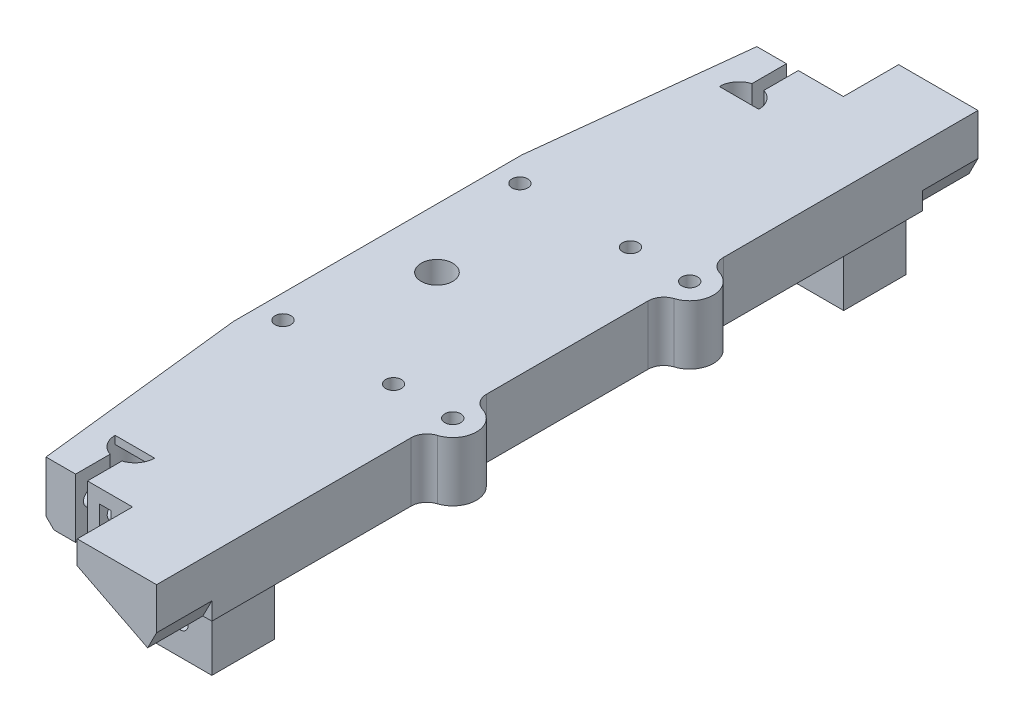
SolidWorks part; units mm, degrees
ref_plane "Płaszczyzna przednia" through (0, 0, 0) normal (0, 0, 1) x (1, 0, 0)
ref_plane "Płaszczyzna górna" through (0, 0, 0) normal (0, 1, 0) x (1, 0, 0)
ref_plane "Płaszczyzna prawa" through (0, 0, 0) normal (1, 0, 0) x (0, 0, -1)
sketch "Szkic1" plane through (0, 0, 0) normal (0, 1, 0) x (1, 0, 0)
  line L0 (-20.5, 36.5) -> (-14.5, 90)
  line L1 (27.5, -90) -> (-14.5, -90)
  line L2 (27.5, -90) -> (27.5, 90)
  line L3 (27.5, 90) -> (-14.5, 90)
  line L4 (-20.5, -36.5) -> (-20.5, 36.5)
  line L5 (27.5, 0) -> (-46.9742, 0) construction
  line L6 (-7, -81.2697) -> (-7, -90)
  line L7 (-20.5, -36.5) -> (-14.5, -90)
  line L8 (-4, -81.2697) -> (-4, -90)
  line L9 (-7, 81.2697) -> (-7, 90)
  line L10 (-4, 81.2697) -> (-4, 90)
  circle A0 centre (-14.5, 30) radius 2
  circle A1 centre (13.5, 30) radius 2
  circle A4 centre (13.5, -30) radius 2
  circle A5 centre (-14.5, -30) radius 2
  circle A6 centre (-5.5, -76.5) radius 5
  circle A7 centre (-5.5, 0) radius 4
  circle A8 centre (-5.5, 76.5) radius 5
  point P0 (0, 0)
  dimension "D7" = 6
  dimension "D10" = 4
  dimension "D11" = 30
  dimension "D12" = 15
  dimension "D13" = 8
  dimension "D16" = 10
  dimension "D1" = 48
  dimension "D2" = 180
  dimension "D3" = 27.5
  dimension "D4" = 90
  dimension "D5" = 42
  dimension "D6" = 73
  dimension "D8" = 28
  dimension "D14" = 13.5
  dimension "D15" = 15
  dimension "D17" = 3
  dimension "D19" = 13.5
  dimension "D20" = 3
extrude "Dodanie-wyciągnięcie1" add sketch "Szkic1" along normal blind 15 contours L2 L5 A7 L4 L7 L1 L6 A6 L8 A5 A4 | L5 L2 L3 L10 A8 L9 L0 L4 A7 A0 A1 region at (4.6975, 0, -43.3979) region at (4.6975, 0, 43.3979)
sketch "Szkic2" plane through (0, 0, 0) normal (0, -1, 0) x (1, 0, 0)
  line L0 (27.5, 90) -> (27.5, -90) construction
  line L1 (25.4, -87.9) -> (9.6, -87.9)
  line L2 (25.4, -87.9) -> (25.4, -72.1)
  line L3 (25.4, -72.1) -> (9.6, -72.1)
  line L4 (9.6, -87.9) -> (9.6, -72.1)
  line L5 (25.4, -87.9) -> (9.6, -72.1) construction
  line L6 (25.4, -72.1) -> (9.6, -87.9) construction
  line L7 (27.5, -90) -> (-4, -90) construction
  point P0 (17.5, -80)
  dimension "D1" = 15.8
  dimension "D2" = 2.1
  dimension "D3" = 2.1
extrude "Dodanie-wyciągnięcie2" add sketch "Szkic2" along normal blind 14
mirror "Lustro1" about plane through (0, 0, 0) normal (0, 0, 1) of "Dodanie-wyciągnięcie2"
sketch "Szkic3" plane through (0, 15, 0) normal (0, 1, 0) x (1, 0, 0)
  line L0 (-10.5, 76.5) -> (-0.5, 76.5)
  line L1 (-10.5, -76.5) -> (-0.5, -76.5)
  arc A0 (-7, 81.2697) -> (-4, 81.2697) centre (-5.5, 76.5) ccw construction
  arc A1 (-4, -81.2697) -> (-7, -81.2697) centre (-5.5, -76.5) ccw construction
  arc A2 (-7, 81.2697) -> (-4, 81.2697) centre (-5.5, 76.5) ccw
  arc A3 (-4, -81.2697) -> (-7, -81.2697) centre (-5.5, -76.5) ccw
  arc M7 (-4, 81.2697) -> (-7, 81.2697) centre (-5.5, 76.5) cw
  arc M15 (-7, -81.2697) -> (-4, -81.2697) centre (-5.5, -76.5) cw
extrude "Dodanie-wyciągnięcie3" add sketch "Szkic3" against normal blind 2 contours L1 M15 | L0 M7 region at (-5.5, 15, -74.3779) region at (-5.5, 15, 74.3779)
sketch "Szkic4" plane through (0, 15, 0) normal (0, 1, 0) x (1, 0, 0)
  circle A0 centre (28.5, -30) radius 2
  circle A1 centre (28.5, 30) radius 2
  circle A2 centre (13.5, 30) radius 2 construction
  circle A3 centre (13.5, -30) radius 2 construction
  circle A4 centre (13.5, 30) radius 2
  circle A5 centre (13.5, -30) radius 2
  circle A6 centre (28.5, -30) radius 6
  circle A7 centre (28.5, 30) radius 6
  line M4 (27.5, -90) -> (27.5, 90)
  dimension "D1" = 4
  dimension "D2" = 4
  dimension "D4" = 12
  dimension "D5" = 12
  dimension "D3" = 15
extrude "Dodanie-wyciągnięcie4" add sketch "Szkic4" against normal blind 15 contours A6 A0 M4 | A7 A1 M4 region at (30.8051, 15, 30) region at (30.8051, 15, -30)
sketch "Szkic5" plane through (0, 15, 0) normal (0, 1, 0) x (1, 0, 0)
  line L16 (27.5, -90) -> (27.5, -35.9161)
  line L17 (27.5, -24.0839) -> (27.5, 24.0839)
  line L18 (27.5, 35.9161) -> (27.5, 90)
  line L19 (27.5, 90) -> (-4, 90)
  line L20 (-4, 90) -> (-4, 81.2697)
  line L21 (-0.5, 76.5) -> (-10.5, 76.5)
  line L22 (-7, 81.2697) -> (-7, 90)
  line L23 (-7, 90) -> (-14.5, 90)
  line L24 (-14.5, 90) -> (-20.5, 36.5)
  line L25 (-20.5, 36.5) -> (-20.5, -36.5)
  line L26 (-20.5, -36.5) -> (-14.5, -90)
  line L27 (-14.5, -90) -> (-7, -90)
  line L28 (-7, -90) -> (-7, -81.2697)
  line L29 (-10.5, -76.5) -> (-0.5, -76.5)
  line L30 (-4, -81.2697) -> (-4, -90)
  line L31 (-4, -90) -> (27.5, -90)
  line L32 (27.5, -90) -> (27.5, -35.9161)
  line L33 (27.5, -24.0839) -> (27.5, 24.0839)
  line L34 (27.5, 35.9161) -> (27.5, 90)
  line L35 (27.5, 90) -> (-4, 90)
  line L36 (-4, 90) -> (-4, 81.2697)
  line L37 (-0.5, 76.5) -> (-10.5, 76.5)
  line L38 (-7, 81.2697) -> (-7, 90)
  line L39 (-7, 90) -> (-14.5, 90)
  line L40 (-14.5, 90) -> (-20.5, 36.5)
  line L41 (-20.5, 36.5) -> (-20.5, -36.5)
  line L42 (-20.5, -36.5) -> (-14.5, -90)
  line L43 (-14.5, -90) -> (-7, -90)
  line L44 (-7, -90) -> (-7, -81.2697)
  line L45 (-10.5, -76.5) -> (-0.5, -76.5)
  line L46 (-4, -81.2697) -> (-4, -90)
  line L47 (-4, -90) -> (27.5, -90)
  arc A0 (27.5, 28.2679) -> (27.5, 31.7321) centre (28.5, 30) ccw construction
  arc A1 (27.5, 28.2679) -> (27.5, 31.7321) centre (28.5, 30) ccw
  arc A2 (27.5, -31.7321) -> (27.5, -28.2679) centre (28.5, -30) ccw construction
  arc A3 (27.5, -31.7321) -> (27.5, -28.2679) centre (28.5, -30) ccw
  circle A4 centre (28.5, 30) radius 2
  circle A5 centre (28.5, -30) radius 2
  arc A6 (27.5, -35.9161) -> (27.5, -24.0839) centre (28.5, -30) ccw
  arc A7 (27.5, 24.0839) -> (27.5, 35.9161) centre (28.5, 30) ccw
  arc A8 (-0.5, 76.5) -> (-4, 81.2697) centre (-5.5, 76.5) ccw
  arc A9 (-7, 81.2697) -> (-10.5, 76.5) centre (-5.5, 76.5) ccw
  arc A10 (-10.5, -76.5) -> (-7, -81.2697) centre (-5.5, -76.5) ccw
  arc A11 (-4, -81.2697) -> (-0.5, -76.5) centre (-5.5, -76.5) ccw
  arc A12 (27.5, -35.9161) -> (27.5, -24.0839) centre (28.5, -30) ccw
  arc A13 (27.5, 24.0839) -> (27.5, 35.9161) centre (28.5, 30) ccw
  arc A14 (-0.5, 76.5) -> (-4, 81.2697) centre (-5.5, 76.5) ccw
  arc A15 (-7, 81.2697) -> (-10.5, 76.5) centre (-5.5, 76.5) ccw
  arc A16 (-10.5, -76.5) -> (-7, -81.2697) centre (-5.5, -76.5) ccw
  arc A17 (-4, -81.2697) -> (-0.5, -76.5) centre (-5.5, -76.5) ccw
  arc M23 (27.5, 31.7321) -> (27.5, 28.2679) centre (28.5, 30) cw
  line M24 (27.5, 28.2679) -> (27.5, 31.7321)
  arc M25 (27.5, -28.2679) -> (27.5, -31.7321) centre (28.5, -30) cw
  line M26 (27.5, -31.7321) -> (27.5, -28.2679)
  dimension "D2" = 4
  dimension "D3" = 4
  dimension "D1" = 0
extrude "Wytnij-wyciągnięcie1" cut sketch "Szkic5" against normal blind 15 contours M25 M26 | A5 M26 | A4 M24 | M23 M24 region at (28.8427, 15, -30) region at (27.09, 15, -30) region at (28.8427, 15, 30) region at (27.09, 15, 30)
fillet "Zaokrąglenie1" radius 4 4 edges at (27.5, 7.5, -35.9161) (27.5, 7.5, -24.0839) (27.5, 7.5, 24.0839) (27.5, 7.5, 35.9161)
chamfer "Sfazowanie1" distance 2 angle 45 3 edges at (-17.5, 0, -63.25) (-17.5, 0, 63.25) (-20.5, 0, 0)
sketch "Szkic6" plane through (0, 0, 87.9) normal (0, 0, 1) x (1, 0, 0)
  line L0 (25.4, -14) -> (25.4, 0) construction
  line L1 (9.6, -14) -> (25.4, -14) construction
  circle A0 centre (17.4, -6) radius 2
  dimension "D1" = 4
  dimension "D2" = 8
  dimension "D3" = 8
extrude "Wytnij-wyciągnięcie2" cut sketch "Szkic6" against normal through all
sketch "Szkic8" plane through (-4, 0, 0) normal (-1, 0, 0) x (0, 0, 1)
  line L0 (90, 15) -> (90, 0) construction
  line L1 (81.2697, 15) -> (90, 15) construction
  circle A0 centre (86, 8) radius 2
  dimension "D1" = 4
  dimension "D2" = 4
  dimension "D3" = 7
extrude "Wytnij-wyciągnięcie3" cut sketch "Szkic8" along normal through all and the other way blind 7
sketch "Szkic9" plane through (-4, 0, 0) normal (-1, 0, 0) x (0, 0, 1)
  circle A0 centre (86, 8) radius 3.5
  dimension "D1" = 7
extrude "Wytnij-wyciągnięcie4" cut sketch "Szkic9" along normal blind 4 from offset 8
sketch "Szkic10" plane through (-4, 0, 0) normal (-1, 0, 0) x (0, 0, 1)
  line L0 (86, 11.4641) -> (90, 11.4641)
  line L1 (86, 11.4641) -> (83, 9.7321)
  line L2 (83, 9.7321) -> (83, 6.2679)
  line L3 (83, 6.2679) -> (86, 4.5359)
  line L4 (86, 4.5359) -> (89, 6.2679)
  line L5 (89, 6.2679) -> (89, 9.7321)
  line L6 (89, 9.7321) -> (86, 11.4641)
  line L7 (90, 15) -> (90, 0) construction
  line L8 (90, 11.4641) -> (90, 4.5359)
  line L9 (90, 4.5359) -> (86, 4.5359)
  circle A0 centre (86, 8) radius 3 construction
  circle M1 centre (86, 8) radius 2
  line M3 (90, 0) -> (90, 15)
  dimension "D1" = 6
extrude "Wytnij-wyciągnięcie5" cut sketch "Szkic10" against normal blind 3 from offset 3 contours L5 L6 L1 L2 L3 L4 M1 | L9 L0 L6 L5 L4 M3 region at (-4, 10.5187, 87.4542) region at (-4, 11.3841, 88) offset against normal yes
mirror "Lustro2" about plane through (0, 0, 0) normal (0, 0, 1) of "Wytnij-wyciągnięcie5", "Wytnij-wyciągnięcie4", "Wytnij-wyciągnięcie3"
sketch "Szkic11" plane through (0, 0, 90) normal (0, 0, 1) x (1, 0, 0)
  line L0 (25.23, 0) -> (7.4099, 9.0798)
  line L1 (27.5, 0) -> (-4, 0) construction
  line L2 (7.4099, 9.0798) -> (9.6799, 13.5348)
  line L3 (9.6799, 13.5348) -> (27.5, 4.455)
  line L4 (27.5, 4.455) -> (25.23, 0)
  line L5 (27.5, 15) -> (27.5, 0) construction
  line L6 (7.4099, 9.0798) -> (7.4099, 15)
  line L7 (27.5, 15) -> (-4, 15) construction
  line L8 (7.4099, 15) -> (27.5, 15)
  line L9 (27.5, 15) -> (27.5, 4.455)
  line M6 (27.5, 0) -> (27.5, 15)
  line M7 (27.5, 15) -> (-4, 15)
  dimension "D1" = 27
  dimension "D2" = 5
  dimension "D3" = 20
extrude "Dodanie-wyciągnięcie5" add sketch "Szkic11" along normal blind 14 contours L4 L3 L2 L0 | L6 L2 L3 M6 M7 region at (17.455, 6.7674, 90) region at (19.926, 11.5347, 90)
sketch "Szkic12" plane through (5.2001, 10.2058, 0) normal (-0.454, -0.891, 0) x (0.891, -0.454, 0)
  line L0 (2.4801, 104) -> (2.4801, 90) construction
  line L1 (16.9801, 91) -> (6.7801, 91)
  line L2 (16.9801, 91) -> (16.9801, 101.2)
  line L3 (16.9801, 101.2) -> (6.7801, 101.2)
  line L4 (6.7801, 91) -> (6.7801, 101.2)
  line L5 (16.9801, 91) -> (6.7801, 101.2) construction
  line L6 (16.9801, 101.2) -> (6.7801, 91) construction
  line L7 (22.4801, 90) -> (2.4801, 90) construction
  point P0 (11.8801, 96.1)
  dimension "D1" = 10.2
  dimension "D2" = 4.3
  dimension "D3" = 1
extrude "Wytnij-wyciągnięcie6" cut sketch "Szkic12" against normal blind 5
mirror "Lustro3" about plane through (0, 0, 0) normal (0, 0, 1) of "Wytnij-wyciągnięcie6", "Dodanie-wyciągnięcie5"
